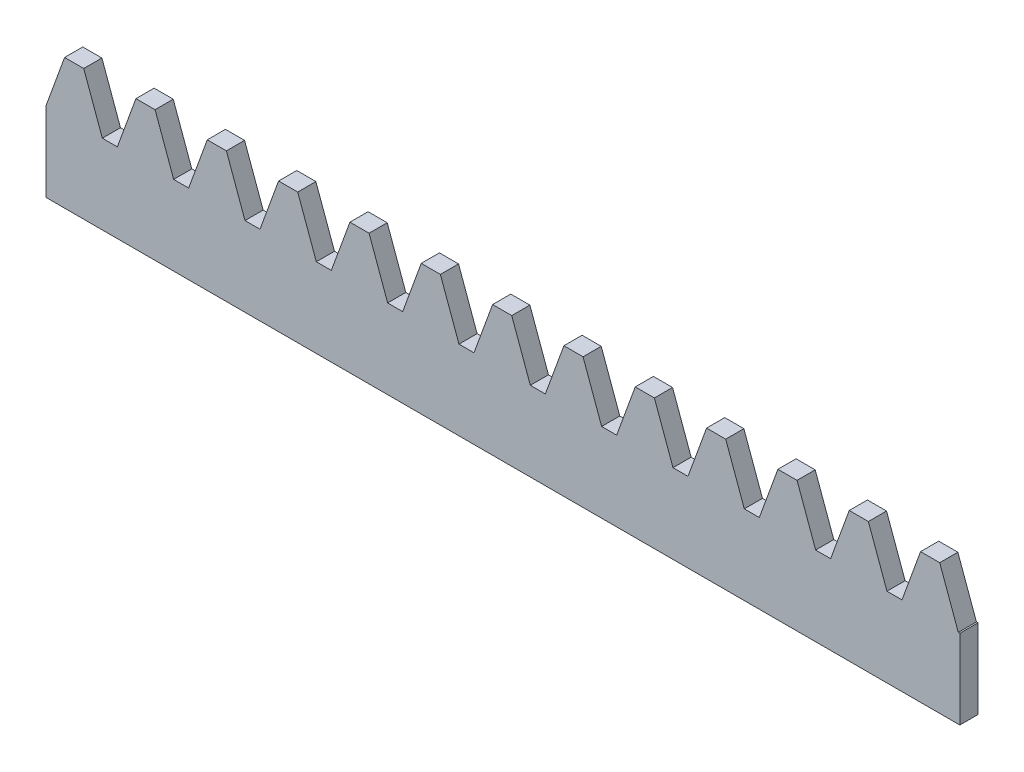
SolidWorks part; units mm, degrees
ref_plane "前视基准面" through (0, 0, 0) normal (0, 0, 1) x (1, 0, 0)
ref_plane "上视基准面" through (0, 0, 0) normal (0, 1, 0) x (1, 0, 0)
ref_plane "右视基准面" through (0, 0, 0) normal (1, 0, 0) x (0, 0, -1)
sketch "草图1" plane through (0, 0, 0) normal (0, 0, 1) x (1, 0, 0)
  line L1 (0, 0) -> (94.2478, 0)
  line L2 (0, 0) -> (0, -10)
  line L3 (0, -10) -> (94.2478, -10)
  line L4 (94.2478, 0) -> (94.2478, -10)
  dimension "D1" = 10
  dimension "L" = 94.2478
extrude "拉伸1" add sketch "草图1" along normal blind 30
sketch "草图2" plane through (0, 0, 30) normal (0, 0, 1) x (1, 0, 0)
  line L0 (0, 0) -> (0.8189, 2.25)
  line L1 (0.8189, 2.25) -> (1.6618, 2.25)
  line L2 (1.6618, 2.25) -> (2.4807, 0)
  line L3 (94.2478, 0) -> (0, 0) construction
  line L4 (0, 0) -> (2.4807, 0)
  line L5 (0.455, 1.25) -> (2.0258, 1.25) construction
  dimension "D2" = 70
  dimension "alpha" = 110
  dimension "ha" = 1
  dimension "hf" = 1.25
  dimension "S" = 1.5708
extrude "拉伸2" add sketch "草图2" against normal up to surface (30 mm away) up to face at (47.1239, -5, 0)
pattern_linear "阵列(线性)1" count 30 spacing 3.1416 along (1, 0, 0) of "拉伸2"
sketch "草图3" plane through (0, 0, 30) normal (0, 0, 1) x (1, 0, 0)
  line L1 (-12.0886, 17.554) -> (115.6309, 17.554)
  line L2 (-12.0886, 17.554) -> (-12.0886, -30.2189)
  line L3 (-12.0886, -30.2189) -> (115.6309, -30.2189)
  line L4 (115.6309, 17.554) -> (115.6309, -30.2189)
extrude "切除-拉伸1" cut sketch "草图3" against normal blind 29.2
sketch "草图4" plane through (0, -10, 0) normal (0, -1, 0) x (1, 0, 0)
  line L1 (-7.7337, 19.6292) -> (109.1312, 19.6292)
  line L2 (-7.7337, 19.6292) -> (-7.7337, -21.7741)
  line L3 (-7.7337, -21.7741) -> (109.1312, -21.7741)
  line L4 (109.1312, 19.6292) -> (109.1312, -21.7741)
extrude "切除-拉伸2" cut sketch "草图4" against normal blind 6.5
sketch "草图5" plane through (94.2478, 0, 0) normal (1, 0, 0) x (0, 0, -1)
  line L1 (-4.0313, 2.415) -> (3.7656, 2.415)
  line L2 (-4.0313, 2.415) -> (-4.0313, -5.7325)
  line L3 (-4.0313, -5.7325) -> (3.7656, -5.7325)
  line L4 (3.7656, 2.415) -> (3.7656, -5.7325)
extrude "切除-拉伸3" cut sketch "草图5" against normal blind 54
equation "\"d\"=\"S@草图2\" * 2"
equation "\"z\"= int(  \"L@草图1\" / (  \"S@草图2\" * 2 ) + 0.5 )"
